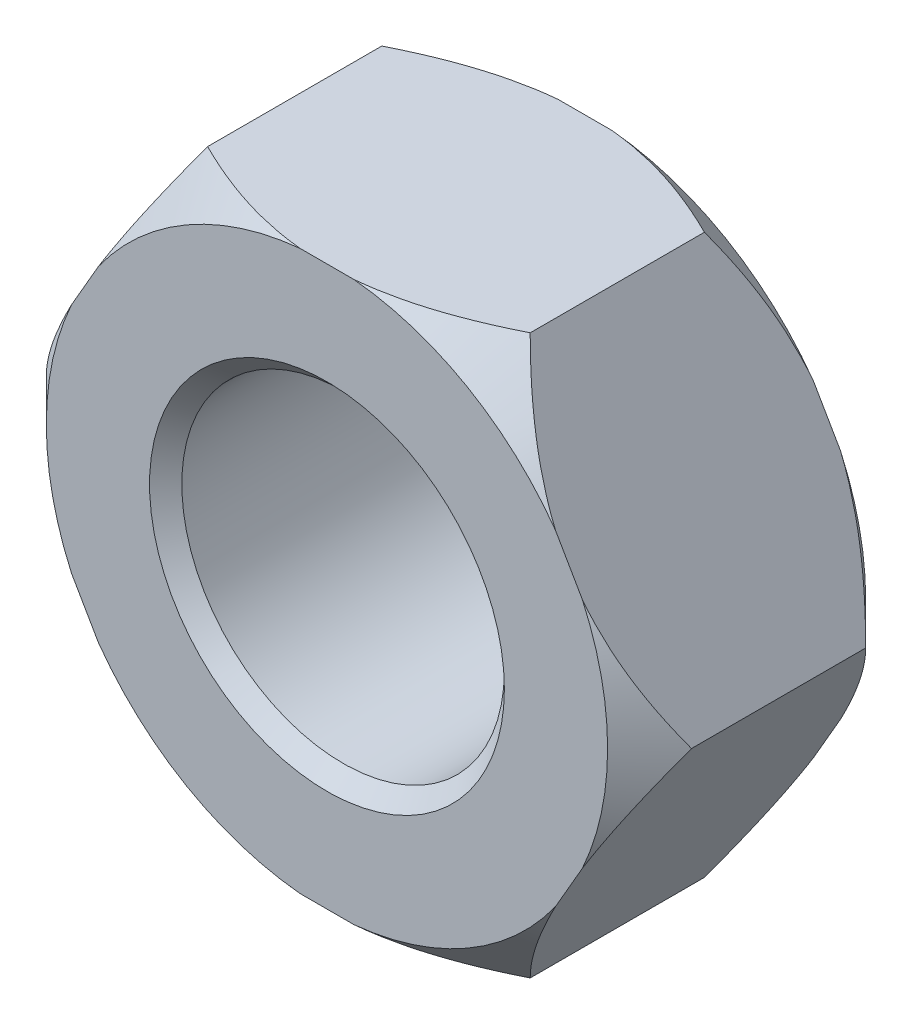
SolidWorks part; units mm, degrees
ref_plane "Front Plane" through (0, 0, 0) normal (0, 0, 1) x (1, 0, 0)
ref_plane "Top Plane" through (0, 0, 0) normal (0, 1, 0) x (1, 0, 0)
ref_plane "Right Plane" through (0, 0, 0) normal (1, 0, 0) x (0, 0, -1)
sketch "Sketch1" plane through (0, 0, 0) normal (0, 0, 1) x (1, 0, 0)
  line L1 (-10, 0) -> (-5, -8.6603)
  line L2 (-5, -8.6603) -> (5, -8.6603)
  line L3 (5, -8.6603) -> (10, 0)
  line L4 (10, 0) -> (5, 8.6603)
  line L5 (5, 8.6603) -> (-5, 8.6603)
  line L6 (-5, 8.6603) -> (-10, 0)
  circle A0 centre (0, 0) radius 10 construction
  dimension "D1" = 20
extrude "Boss-Extrude1" add sketch "Sketch1" along normal mid plane 8
sketch "Sketch2" plane through (0, 0, -4) normal (0, 0, 1) x (1, 0, 0)
  circle A0 centre (0, 0) radius 5
  dimension "D1" = 10
extrude "Cut-Extrude1" cut sketch "Sketch2" along normal through all
cosmetic thread "Cosmetic Thread1" parameters "D2"=12
sketch "Sketch8" plane through (0, 0, 0) normal (0, 1, 0) x (1, 0, 0)
  line L0 (-8.6, -4.1) -> (-10.1, -4.1)
  line L1 (-10.1, -4.1) -> (-10.1, -2.6)
  line L2 (-10.1, -2.6) -> (-8.6, -4.1)
  line L4 (-10, -4) -> (-10, 4) construction
  line L5 (-5, -4) -> (-10, -4) construction
  dimension "D1" = 1.5
  dimension "D2" = 1.5
  dimension "D3" = 0.1
  dimension "D4" = 0.1
ref_axis "Axis1" through (0, 0, -7.705) along (0, 0, 1)
revolve "Cut-Revolve1" cut sketch "Sketch8" angle 360 about axis through (0, 0, -7.705) along (0, 0, 1)
ref_axis "Axis2" through (0, 0, -7.7832) along (0, 0, 1)
mirror "Mirror1" about plane through (0, 0, 0) normal (0, 0, 1) of "Cut-Revolve1"
chamfer "Chamfer1" distance 0.5 angle 45 2 edges at (5, 0, -4) (5, 0, 4)
